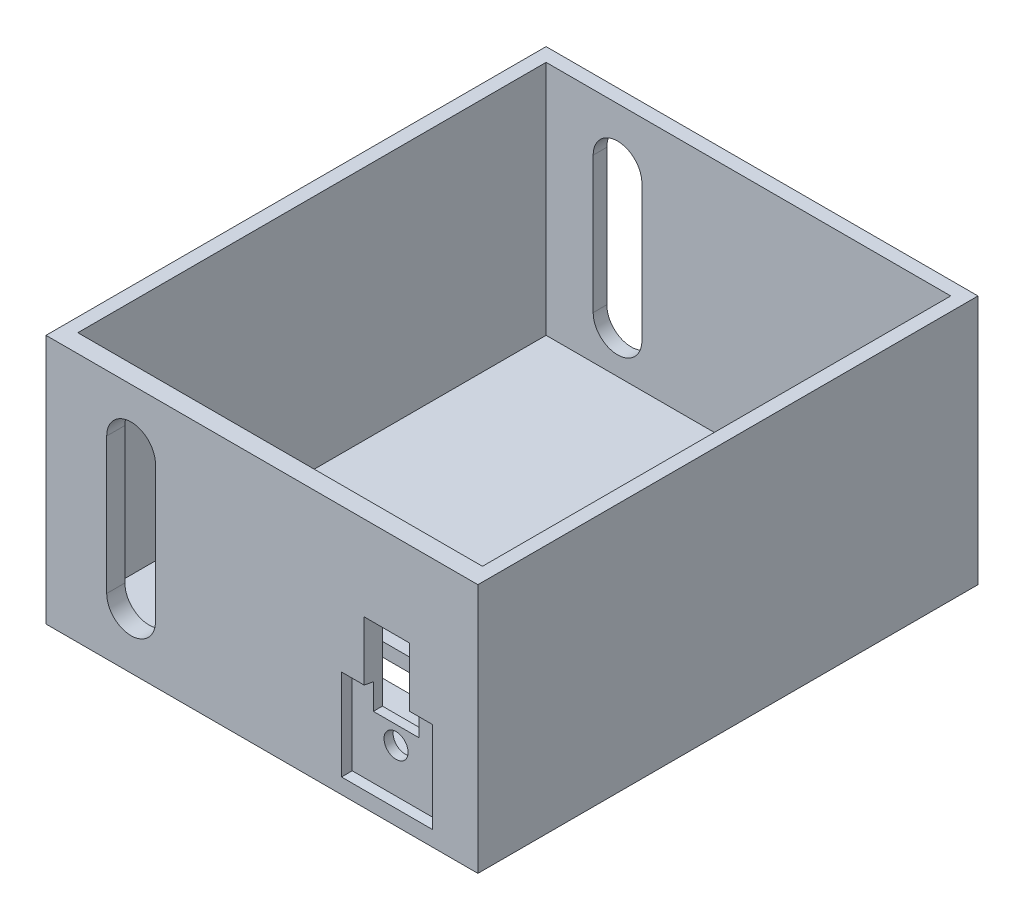
SolidWorks part; units mm, degrees
ref_plane "前视基准面" through (0, 0, 0) normal (0, 0, 1) x (1, 0, 0)
ref_plane "上视基准面" through (0, 0, 0) normal (0, 1, 0) x (1, 0, 0)
ref_plane "右视基准面" through (0, 0, 0) normal (1, 0, 0) x (0, 0, -1)
sketch "铝材侧" plane through (0, 0, 0) normal (0, 0, 1) x (1, 0, 0)
  line L0 (37.2315, -7.468) -> (37.2315, 43.9088) construction
  line L1 (-37.7685, 24.165) -> (57.2315, 24.165)
  line L2 (-37.7685, 24.165) -> (-37.7685, -30.835)
  line L3 (-37.7685, -30.835) -> (57.2315, -30.835)
  line L4 (57.2315, 24.165) -> (57.2315, -30.835)
  line L5 (27.2315, -7.468) -> (47.2315, -7.468)
  line L6 (27.2315, -7.468) -> (27.2315, -27.468)
  line L7 (27.2315, -27.468) -> (47.2315, -27.468)
  line L8 (47.2315, -7.468) -> (47.2315, -27.468)
  line L9 (32.2315, 5.532) -> (42.2315, 5.532)
  line L10 (32.2315, 5.532) -> (32.2315, -13.468)
  line L11 (32.2315, -13.468) -> (42.2315, -13.468)
  line L12 (42.2315, 5.532) -> (42.2315, -13.468)
  circle A0 centre (37.2315, -17.468) radius 2.65
  dimension "D5" = 20
  dimension "D1" = 20
  dimension "D2" = 20
  dimension "D3" = 10
  dimension "D4" = 10
  dimension "D6" = 14
  dimension "D7" = 10
  dimension "D8" = 19
  dimension "D9" = 13.367
  dimension "D10" = 95
  dimension "D11" = 55
extrude "凸台-拉伸2" add sketch "铝材侧" against normal blind 110 contours L1 L4 L3 L2
sketch "顶" plane through (0, 24.165, 0) normal (0, 1, 0) x (1, 0, 0)
  line L0 (-37.7685, 110) -> (57.2315, 110) construction
  line L1 (-34.7685, 107) -> (54.2315, 107)
  line L2 (-34.7685, 107) -> (-34.7685, 4)
  line L3 (-34.7685, 4) -> (54.2315, 4)
  line L4 (54.2315, 107) -> (54.2315, 4)
  line L5 (57.2315, 110) -> (57.2315, 0) construction
  line L6 (-37.7685, 110) -> (-37.7685, 0) construction
  line L7 (-37.7685, 0) -> (57.2315, 0) construction
  dimension "D1" = 3
  dimension "D2" = 3
  dimension "D3" = 3
  dimension "D4" = 4
extrude "切除-拉伸1" cut sketch "顶" against normal blind 52 contours L2 L1 L4 L3
extrude "切除-拉伸2" cut sketch "铝材侧<4>" against normal blind 10 contours L9 L12 L11 L10
sketch "铝材侧<4>" plane through (0, 0, 0) normal (0, 0, 1) x (1, 0, 0) same geometry as "铝材侧"
extrude "切除-拉伸3" cut sketch "铝材侧<5>" against normal blind 10 contours A0
sketch "铝材侧<5>" plane through (0, 0, 0) normal (0, 0, 1) x (1, 0, 0) same geometry as "铝材侧"
extrude "切除-拉伸4" cut sketch "铝材侧<6>" against normal blind 2 draft 10 contours L8 L7 L6 L5
sketch "铝材侧<6>" plane through (0, 0, 0) normal (0, 0, 1) x (1, 0, 0) same geometry as "铝材侧"
sketch "草图7" plane through (0, -30.835, 0) normal (0, -1, 0) x (1, 0, 0)
  line L0 (-12.712, -27.203) -> (32.1751, -27.203) construction
  line L1 (-12.712, -23.7026) -> (32.1751, -23.7026)
  line L2 (9.7315, 0) -> (9.7315, -84.4598) construction
  line L3 (-37.7685, 0) -> (57.2315, 0) construction
  line L4 (-37.7685, -55) -> (77.7412, -55) construction
  line L5 (-37.7685, -110) -> (-37.7685, 0) construction
  line L6 (-12.712, -30.7033) -> (32.1751, -30.7033)
  circle A0 centre (9.7315, -55) radius 2.65
  arc A1 (-12.712, -23.7026) -> (-12.712, -30.7033) centre (-12.712, -27.203) ccw
  arc A2 (32.1751, -30.7033) -> (32.1751, -23.7026) centre (32.1751, -27.203) ccw
  point P12 (9.7315, -27.203)
  point P17 (0, 0)
  dimension "D1" = 0
  dimension "D2" = 0
extrude "切除-拉伸5" cut sketch "草图7" against normal blind 5
sketch "草图8" plane through (0, 0, -110) normal (0, 0, -1) x (-1, 0, 0)
  line L0 (19.0561, 11.665) -> (19.0561, -18.335) construction
  line L1 (24.4151, 11.665) -> (24.4151, -18.335)
  line L2 (13.6971, 11.665) -> (13.6971, -18.335)
  line L3 (37.7685, -3.335) -> (67.7685, -3.335) construction
  line L4 (37.7685, 24.165) -> (37.7685, -30.835) construction
  arc A0 (24.4151, 11.665) -> (13.6971, 11.665) centre (19.0561, 11.665) ccw
  arc A1 (13.6971, -18.335) -> (24.4151, -18.335) centre (19.0561, -18.335) ccw
  point P2 (19.0561, -3.335)
  dimension "D1" = 0
  dimension "D2" = 30
extrude "切除-拉伸6" cut sketch "草图8" against normal blind 130
